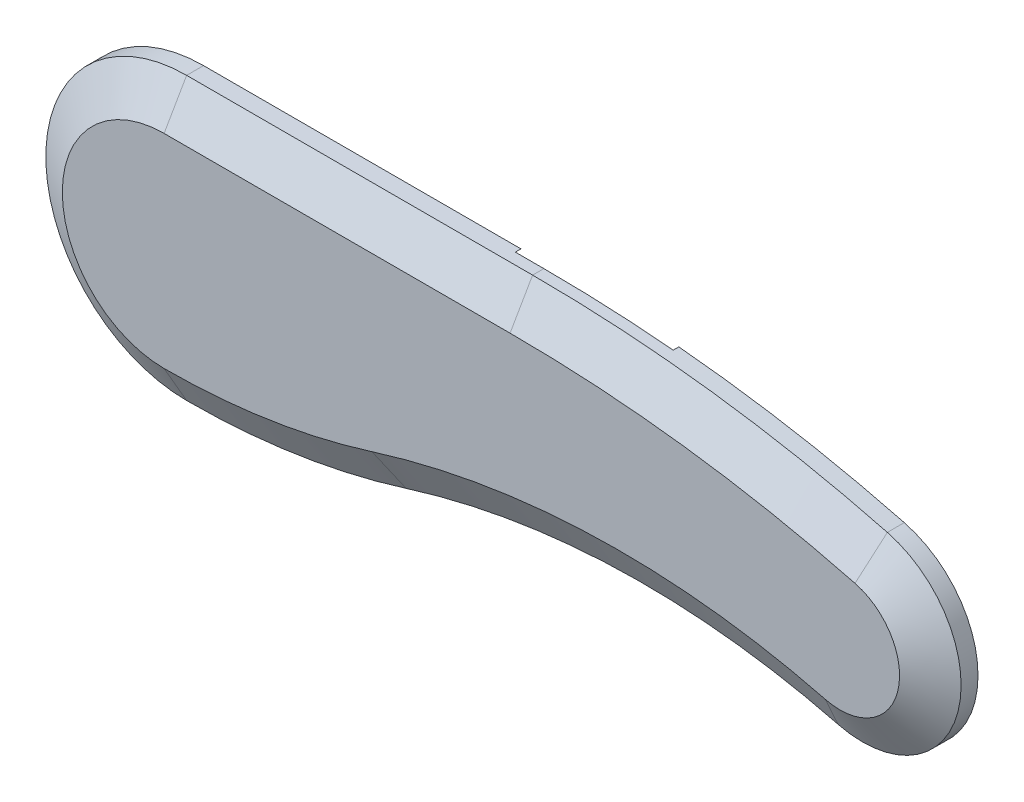
SolidWorks part; units mm, degrees
ref_plane "Front Plane" through (0, 0, 0) normal (0, 0, 1) x (1, 0, 0)
ref_plane "Top Plane" through (0, 0, 0) normal (0, 1, 0) x (1, 0, 0)
ref_plane "Right Plane" through (0, 0, 0) normal (1, 0, 0) x (0, 0, -1)
sketch "Sketch1" plane through (0, 0, 0) normal (0, 0, 1) x (1, 0, 0)
  line L0 (0, 0) -> (120, 0) construction
  line L1 (0, 0) -> (0, -25) construction
  line L2 (0, 25) -> (61.4231, 25)
  circle A0 centre (0, 0) radius 25
  circle A2 centre (120, 0) radius 17.5
  arc A3 (61.4231, 25) -> (124.409, 16.9355) centre (61.4231, -225) cw
  arc A4 (0, -25) -> (38.9734, -19.0205) centre (0, 105) ccw
  arc A5 (38.9734, -19.0205) -> (115.6605, -16.9534) centre (80.9448, -152.5809) cw
  dimension "D2" = 50
  dimension "D4" = 35
  dimension "D5" = 250
  dimension "D6" = 140
  dimension "D7" = 130
  dimension "D1" = 120
  dimension "D3" = 0
extrude "Boss-Extrude1" add sketch "Sketch1" along normal blind 7 contours A0 L0 A2 A3 L2 | L0 A0 A4 A5 A2 | A0 | A2 region at (60.7118, 4.4003, 0) region at (0, 0, 0) region at (120, 0, 0)
chamfer "Chamfer1" distance 4 angle 60 6 edges at (19.7147, -23.4964, 7) (-25, 0, 7) (30.7116, 25, 7) (93.1732, 22.9757, 7) (136.9445, -4.3742, 7) (77.1726, -12.6318, 7) first distance on face at (19.6007, -22.7533, 3.5) first distance on face at (-12.5, 0, 3.5) first distance on face at (30.7116, 25, 3.5) first distance on face at (93.0446, 21.9717, 3.5) first distance on face at (128.4896, -2.1916, 3.5) first distance on face at (77.2448, -15.3094, 3.5)
sketch "Sketch3" plane through (0, 0, 0) normal (0, 0, -1) x (-1, 0, 0)
  circle A0 centre (0, 0) radius 8.5
  circle A1 centre (-120, 0) radius 8.5
  dimension "D1" = 17
  dimension "D2" = 17
extrude "Cut-Extrude2" cut sketch "Sketch3" against normal blind 4
ref_plane "Plane1" through (0, 0, 2.5) normal (0, 0, -1) x (-1, 0, 0)
sketch "Sketch5" plane through (0, 0, 2.5) normal (0, 0, -1) x (-1, 0, 0)
  line L0 (0, 0) -> (-60, 0) construction
  line L1 (0, 0) -> (-83.9535, 13.2969) construction
  line L2 (0, 0) -> (-30.0702, -10.9446) construction
  line L3 (-86.0464, 16.9219) -> (-73.7677, 16.9219)
  line L4 (-81.8606, 9.6719) -> (-79.7677, 13.2969)
  line L5 (-79.7677, 13.2969) -> (-81.8606, 16.9219)
  line L6 (-81.8606, 16.9219) -> (-86.0464, 16.9219)
  line L7 (-86.0464, 16.9219) -> (-88.1393, 13.2969)
  line L8 (-88.1393, 13.2969) -> (-86.0464, 9.6719)
  line L9 (-86.0464, 9.6719) -> (-81.8606, 9.6719)
  line L10 (-57.9071, -3.625) -> (-55.8142, 0)
  line L11 (-55.8142, 0) -> (-57.9071, 3.625)
  line L12 (-57.9071, 3.625) -> (-62.0929, 3.625)
  line L13 (-62.0929, 3.625) -> (-64.1858, 0)
  line L14 (-64.1858, 0) -> (-62.0929, -3.625)
  line L15 (-62.0929, -3.625) -> (-57.9071, -3.625)
  line L16 (-27.9773, -14.5696) -> (-25.8844, -10.9446)
  line L17 (-25.8844, -10.9446) -> (-27.9773, -7.3196)
  line L18 (-27.9773, -7.3196) -> (-32.1631, -7.3196)
  line L19 (-32.1631, -7.3196) -> (-34.256, -10.9446)
  line L20 (-34.256, -10.9446) -> (-32.1631, -14.5696)
  line L21 (-32.1631, -14.5696) -> (-27.9773, -14.5696)
  line L22 (-86.0464, 9.6719) -> (-73.7677, 9.6719)
  line L23 (-73.7677, 16.9219) -> (-73.7677, 9.6719) construction
  line L24 (-62.0929, 3.625) -> (-49.8142, 3.625)
  line L25 (-62.0929, -3.625) -> (-49.8142, -3.625)
  line L26 (-49.8142, 3.625) -> (-49.8142, -3.625) construction
  line L27 (-32.1631, -7.3196) -> (-19.8844, -7.3196)
  line L28 (-32.1631, -14.5696) -> (-19.8844, -14.5696)
  line L29 (-19.8844, -14.5696) -> (-19.8844, -7.3196) construction
  circle A0 centre (-83.9535, 13.2969) radius 3.625 construction
  circle A1 centre (-60, 0) radius 3.625 construction
  circle A2 centre (-30.0702, -10.9446) radius 3.625 construction
  circle A3 centre (-73.7677, 13.2969) radius 6
  circle A4 centre (-49.8142, 0) radius 6
  circle A5 centre (-19.8844, -10.9446) radius 6
  circle A6 centre (-83.9535, 13.2969) radius 2.125
  circle A7 centre (-60, 0) radius 2.125
  circle A8 centre (-30.0702, -10.9446) radius 2.125
  dimension "D7" = 12
  dimension "D8" = 4.25
  dimension "D1" = 20
  dimension "D2" = 9
  dimension "D3" = 85
  dimension "D4" = 60
  dimension "D5" = 32
  dimension "D6" = 7.25
extrude "Cut-Extrude3" cut sketch "Sketch5" against normal blind 3.5 contours L8 L9 L4 L5 L3 L7 | A3 | A3 L3 L5 | A3 L4 L22 | L14 L15 L10 L11 L12 L13 | A4 L24 L11 | A4 L10 L25 | A4 | A5 | A5 L16 L28 | A5 L27 L17 | L20 L21 L16 L17 L18 L19 | A7 | A8 | A6 region at (83.9535, 16.8112, 2.5) region at (80.1796, 15.8006, 2.5) region at (73.7677, 13.2969, 2.5) region at (80.1796, 10.7933, 2.5) region at (60, -3.5143, 2.5) region at (56.2261, -2.5037, 2.5) region at (56.2261, 2.5037, 2.5) region at (49.8142, 0, 2.5) region at (30.0702, -14.4589, 2.5) region at (26.2963, -13.4483, 2.5) region at (26.2963, -8.441, 2.5) region at (19.8844, -10.9446, 2.5) region at (60, 0, 2.5) region at (30.0702, -10.9446, 2.5)
extrude "Cut-Extrude4" cut sketch "Sketch5<3>" along normal through all contours A3 | A4 | A5 | A6 | A7 | A8 region at (73.7677, 13.2969, 2.5) region at (49.8142, 0, 2.5) region at (19.8844, -10.9446, 2.5) region at (83.9535, 13.2969, 2.5) region at (60, 0, 2.5) region at (30.0702, -10.9446, 2.5)
sketch "Sketch5<3>" plane through (0, 0, 2.5) normal (0, 0, -1) x (-1, 0, 0) same geometry as "Sketch5"
chamfer "Chamfer2" distance 0.5 angle 70 3 edges at (67.7677, 13.2969, 6) (13.8844, -10.9446, 6) (43.8142, 0, 6) first distance on face at (76.1583, 13.2969, 4.25) first distance on face at (22.2749, -10.9446, 4.25) first distance on face at (52.2048, 0, 4.25)
sketch "Sketch7" plane through (0, 0, 0) normal (0, 0, -1) x (-1, 0, 0)
  circle A0 centre (0, 0) radius 9.5
  circle A1 centre (0, 0) radius 8.5 construction
  circle A2 centre (0, 0) radius 8.5
  circle A3 centre (-120, 0) radius 8.5 construction
  circle A4 centre (-120, 0) radius 8.5
  circle A5 centre (-120, 0) radius 9.5
  dimension "D1" = 1
  dimension "D2" = 1
extrude "Boss-Extrude2" add sketch "Sketch7" along normal blind 0.5
sketch "Sketch8" plane through (0, 0, 0) normal (0, 0, -1) x (-1, 0, 0)
  line L0 (-91.0061, -1.4841) -> (-79.8556, -10.8405) construction
  line L1 (-13.4637, -10.2418) -> (-53.2327, 23.1284) construction
  line L2 (-58.375, 25) -> (-61.4231, 25) construction
  line L3 (-93.3813, 7.3804) -> (-89.1932, 18.8872) construction
  line L4 (-91.0061, -1.4841) -> (-79.8556, -10.8405)
  line L5 (-13.4637, -10.2418) -> (-53.2327, 23.1284)
  line L6 (-58.375, 25) -> (-61.4231, 25)
  line L7 (-93.3813, 7.3804) -> (-89.1932, 18.8872)
  line L8 (-91.1668, -1.6756) -> (-80.0163, -11.032)
  line L9 (-93.6163, 7.4659) -> (-89.4281, 18.9727)
  line L10 (-58.375, 25.25) -> (-61.4231, 25.25)
  line L11 (-13.303, -10.0503) -> (-53.072, 23.3199)
  arc A0 (-10.6159, -15.9715) -> (-13.4637, -10.2418) centre (-18.606, -16.3702) ccw construction
  arc A1 (-19.8261, -23.4793) -> (-10.6159, -15.9715) centre (-18.606, -15.5729) ccw construction
  arc A2 (-38.9734, -19.0205) -> (-19.8261, -23.4793) centre (0, 105) ccw construction
  arc A3 (-38.9734, -19.0205) -> (-75.0501, -12.7051) centre (-80.9448, -152.5809) ccw construction
  arc A4 (-79.8556, -10.8405) -> (-75.0501, -12.7051) centre (-74.7133, -4.7122) ccw construction
  arc A5 (-93.3813, 7.3804) -> (-91.0061, -1.4841) centre (-85.8638, 4.6442) ccw construction
  arc A6 (-53.2327, 23.1284) -> (-58.375, 25) centre (-58.375, 17) ccw construction
  arc A7 (-82.3452, 24.123) -> (-89.1932, 18.8872) centre (-81.6757, 16.1511) ccw construction
  arc A8 (-61.4231, 25) -> (-82.3452, 24.123) centre (-61.4231, -225) ccw construction
  arc A9 (-10.6159, -15.9715) -> (-13.4637, -10.2418) centre (-18.606, -16.3702) ccw
  arc A10 (-19.8261, -23.4793) -> (-10.6159, -15.9715) centre (-18.606, -15.5729) ccw
  arc A11 (-38.9734, -19.0205) -> (-19.8261, -23.4793) centre (0, 105) ccw
  arc A12 (-38.9734, -19.0205) -> (-75.0501, -12.7051) centre (-80.9448, -152.5809) ccw
  arc A13 (-79.8556, -10.8405) -> (-75.0501, -12.7051) centre (-74.7133, -4.7122) ccw
  arc A14 (-93.3813, 7.3804) -> (-91.0061, -1.4841) centre (-85.8638, 4.6442) ccw
  arc A15 (-53.2327, 23.1284) -> (-58.375, 25) centre (-58.375, 17) ccw
  arc A16 (-82.3452, 24.123) -> (-89.1932, 18.8872) centre (-81.6757, 16.1511) ccw
  arc A17 (-61.4231, 25) -> (-82.3452, 24.123) centre (-61.4231, -225) ccw
  arc A18 (-39.0484, -19.259) -> (-75.0606, -12.9549) centre (-80.9448, -152.5809) ccw
  arc A19 (-80.0163, -11.032) -> (-75.0606, -12.9549) centre (-74.7133, -4.7122) ccw
  arc A20 (-93.6163, 7.4659) -> (-91.1668, -1.6756) centre (-85.8638, 4.6442) ccw
  arc A21 (-82.3661, 24.3721) -> (-89.4281, 18.9727) centre (-81.6757, 16.1511) ccw
  arc A22 (-61.4231, 25.25) -> (-82.3661, 24.3721) centre (-61.4231, -225) ccw
  arc A23 (-53.072, 23.3199) -> (-58.375, 25.25) centre (-58.375, 17) ccw
  arc A24 (-10.3656, -15.9715) -> (-13.303, -10.0503) centre (-18.606, -16.3702) ccw
  arc A25 (-19.8642, -23.7264) -> (-10.3656, -15.9715) centre (-18.606, -15.5729) ccw
  arc A26 (-39.0484, -19.259) -> (-19.8642, -23.7264) centre (0, 105) ccw
  circle M16 centre (-19.8844, -10.9446) radius 6
  arc M21 (-38.9734, -19.0205) -> (0, -25) centre (0, 105) ccw
  line M23 (0, 25) -> (-61.4231, 25)
  arc M24 (-61.4231, 25) -> (-124.409, 16.9355) centre (-61.4231, -225) ccw
  arc M26 (-115.6605, -16.9534) -> (-38.9734, -19.0205) centre (-80.9448, -152.5809) cw
  dimension "D1" = 0.25
extrude "Cut-Extrude5" cut sketch "Sketch8" against normal blind 1 contours A23 L10 A22 A21 M23 M24 | L11 A23 A15 L5 M23 M16 | L11 L5 M16 | A25 A24 L11 L5 A9 A10 M21 M16 | A18 A26 A25 A19 M21 M26 | A21 L9 A20 L8 A19 A13 L4 A14 L7 A16 M24 M26 | A13 A12 A11 A10 A9 L5 A15 L6 A17 A16 L7 A14 L4 region at (85.4575, -6.1941, 0) region at (56.8148, -14.7373, 0) region at (70.3826, 24.8447, 0) region at (13.4425, -21.9072, 0) region at (38.0386, 10.4957, 0) region at (16.8063, -7.2764, 0)
